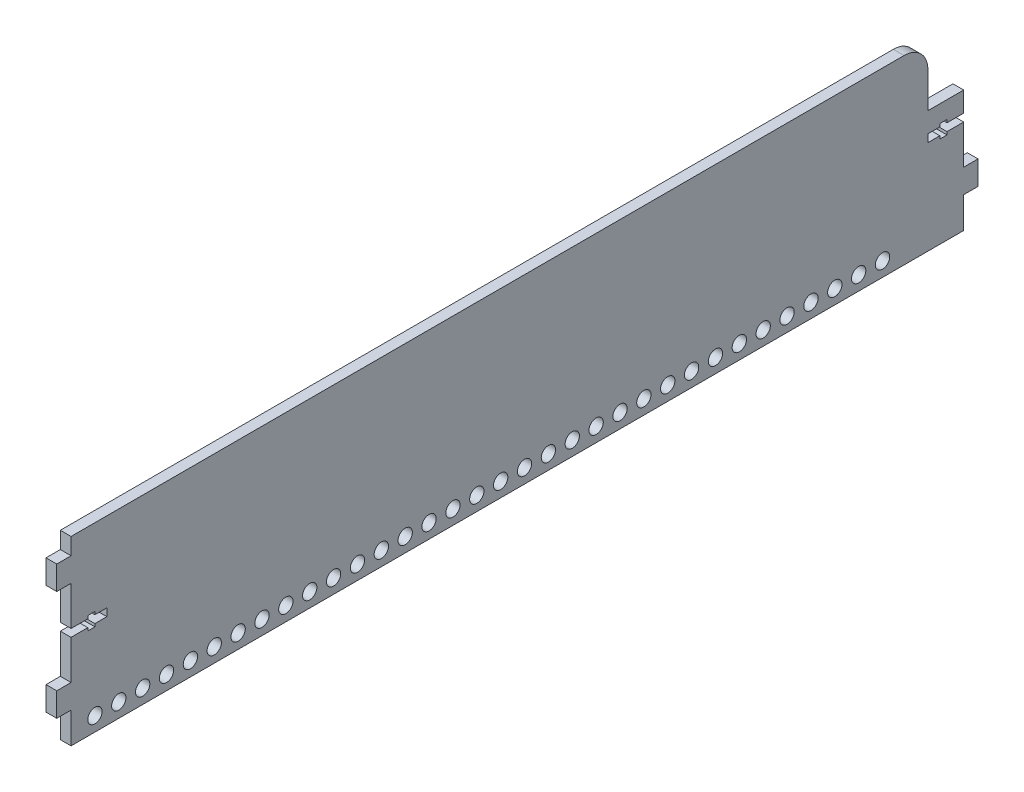
SolidWorks part; units mm, degrees
ref_plane "Front Plane" through (0, 0, 0) normal (0, 0, 1) x (1, 0, 0)
ref_plane "Top Plane" through (0, 0, 0) normal (0, 1, 0) x (1, 0, 0)
ref_plane "Right Plane" through (0, 0, 0) normal (1, 0, 0) x (0, 0, -1)
sketch "Sketch1" plane through (0, 0, 0) normal (1, 0, 0) x (0, 0, -1)
  line L1 (-187, -40) -> (187, -40)
  line L2 (-187, -40) -> (-187, 40)
  line L3 (-187, 40) -> (187, 40)
  line L4 (187, -40) -> (187, 40)
  line L5 (-187, -40) -> (187, 40) construction
  line L6 (-187, 40) -> (187, -40) construction
  point P0 (0, 0)
  dimension "D1" = 80
  dimension "D2" = 374
extrude "Boss-Extrude1" add sketch "Sketch1" along normal blind 4.5
sketch "Sketch4" plane through (0, 0, 187) normal (0, 0, 1) x (1, 0, 0)
  line L1 (4.5, 29) -> (0, 29) construction
  line L2 (4.5, 19) -> (4.5, 29) construction
  line L3 (0, 29) -> (0, 19) construction
  line L4 (0, 19) -> (4.5, 19) construction
  line L7 (4.5, -17) -> (0, -17) construction
  line L8 (4.5, -27) -> (4.5, -17) construction
  line L9 (0, -17) -> (0, -27) construction
  line L10 (0, -27) -> (4.5, -27) construction
  line L13 (4.5, 29) -> (0, 29)
  line L14 (4.5, 19) -> (4.5, 29)
  line L15 (0, 29) -> (0, 19)
  line L16 (0, 19) -> (4.5, 19)
  line L17 (4.5, -17) -> (0, -17)
  line L18 (4.5, -27) -> (4.5, -17)
  line L19 (0, -17) -> (0, -27)
  line L20 (0, -27) -> (4.5, -27)
extrude "Boss-Extrude2" add sketch "Sketch4" along normal blind 6
sketch "Sketch5" plane through (0, 0, 0) normal (-1, 0, 0) x (0, 0, 1)
  line L0 (187, 19) -> (187, -17) construction
  line L7 (0, 0) -> (0, -20.5925) construction
  line L8 (-187, 2.6) -> (-180, 2.6)
  line L9 (-177, 3.8) -> (-180, 3.8)
  line L10 (-177, 2.6) -> (-172, 2.6)
  line L11 (-172, -0.6) -> (-172, 2.6)
  line L12 (-177, -0.6) -> (-172, -0.6)
  line L13 (-177, -1.8) -> (-180, -1.8)
  line L14 (-187, -0.6) -> (-180, -0.6)
  line L15 (-180, -1.8) -> (-180, -0.6)
  line L16 (-180, 2.6) -> (-180, 3.8)
  line L17 (-177, 2.6) -> (-177, 3.8)
  line L18 (-177, -1.8) -> (-177, -0.6)
  line L19 (193, -0.6) -> (193, 2.6) construction
  line L20 (193, -0.6) -> (193, 2.6)
  line L21 (193, 1) -> (146.4296, 1) construction
  line L25 (187, -0.6) -> (187, 2.6)
  line L26 (177, -1.8) -> (177, -0.6)
  line L27 (177, 2.6) -> (177, 3.8)
  line L28 (180, 2.6) -> (180, 3.8)
  line L29 (180, -1.8) -> (180, -0.6)
  line L30 (187, -0.6) -> (180, -0.6)
  line L31 (177, -1.8) -> (180, -1.8)
  line L32 (177, -0.6) -> (172, -0.6)
  line L33 (172, -0.6) -> (172, 2.6)
  line L34 (177, 2.6) -> (172, 2.6)
  line L35 (177, 3.8) -> (180, 3.8)
  line L36 (187, 2.6) -> (180, 2.6)
  line L37 (-187, -0.6) -> (-187, 2.6)
  line L38 (-193, -0.6) -> (-193, 2.6)
  point P0 (187, 1)
  dimension "D1" = 15
  dimension "D2" = 5.6
  dimension "D3" = 3.2
  dimension "D4" = 7
  dimension "D5" = 3
extrude "Cut-Extrude3" cut sketch "Sketch5" against normal up to next contours L25 L36 L28 L35 L27 L34 L33 L32 L26 L31 L29 L30 | L37 L14 L15 L13 L18 L12 L11 L10 L17 L9 L16 L8 region at (0, 1, -179.3696) region at (0, 1, 179.3696)
sketch "Sketch7" plane through (0, 0, -187) normal (0, 0, -1) x (-1, 0, 0)
  line L6 (-4.5, -17) -> (0, -17)
  line L7 (-4.5, -17) -> (-4.5, -27)
  line L8 (-4.5, -27) -> (0, -27)
  line L9 (0, -17) -> (0, -27)
  line L15 (-4.5, -40) -> (-4.5, -0.6) construction
  line L16 (0, -40) -> (0, -0.6) construction
  line L17 (-4.5, -17) -> (0, -17) construction
  line L18 (0, -27) -> (-4.5, -27) construction
extrude "Boss-Extrude3" add sketch "Sketch7" along normal blind 6
sketch "Sketch8" plane through (0, 40, 0) normal (0, 1, 0) x (1, 0, 0)
  line L1 (0, 187) -> (4.5, 187)
  line L2 (0, 187) -> (0, -187)
  line L3 (0, -187) -> (4.5, -187)
  line L4 (4.5, 187) -> (4.5, -187)
extrude "Cut-Extrude4" cut sketch "Sketch8" against normal blind 4
sketch "Sketch9" plane through (0, 36, 0) normal (0, 1, 0) x (1, 0, 0)
  line L0 (0, 187) -> (0, -187) construction
  line L1 (0, 187) -> (4.5, 187)
  line L2 (0, 187) -> (0, 172)
  line L3 (0, 172) -> (4.5, 172)
  line L4 (4.5, 187) -> (4.5, 172)
  line L5 (4.5, -187) -> (4.5, 187) construction
  dimension "D2" = 15
extrude "Cut-Extrude5" cut sketch "Sketch9" against normal blind 25
fillet "Fillet1" radius 10 1 edges at (2.25, 36, -172)
sketch "Sketch10" plane through (0, 0, 0) normal (-1, 0, 0) x (0, 0, 1)
  line L0 (187, -40) -> (-187, -40) construction
  line L1 (187, -27) -> (187, -40) construction
  circle A0 centre (177, -34) radius 3
  circle A1 centre (167, -34) radius 3
  circle A2 centre (157, -34) radius 3
  circle A3 centre (147, -34) radius 3
  circle A4 centre (137, -34) radius 3
  circle A5 centre (127, -34) radius 3
  circle A6 centre (117, -34) radius 3
  circle A7 centre (107, -34) radius 3
  circle A8 centre (97, -34) radius 3
  circle A9 centre (87, -34) radius 3
  circle A10 centre (77, -34) radius 3
  circle A11 centre (67, -34) radius 3
  circle A12 centre (57, -34) radius 3
  circle A13 centre (47, -34) radius 3
  circle A14 centre (37, -34) radius 3
  circle A15 centre (27, -34) radius 3
  circle A16 centre (17, -34) radius 3
  circle A17 centre (7, -34) radius 3
  circle A18 centre (-3, -34) radius 3
  circle A19 centre (-13, -34) radius 3
  circle A20 centre (-23, -34) radius 3
  circle A21 centre (-33, -34) radius 3
  circle A22 centre (-43, -34) radius 3
  circle A23 centre (-53, -34) radius 3
  circle A24 centre (-63, -34) radius 3
  circle A25 centre (-73, -34) radius 3
  circle A26 centre (-83, -34) radius 3
  circle A27 centre (-93, -34) radius 3
  circle A28 centre (-103, -34) radius 3
  circle A29 centre (-113, -34) radius 3
  circle A30 centre (-123, -34) radius 3
  circle A31 centre (-133, -34) radius 3
  circle A32 centre (-143, -34) radius 3
  circle A33 centre (-153, -34) radius 3
  dimension "D1" = 6
  dimension "D2" = 6
  dimension "D3" = 10
  dimension "D4" = 34
extrude "Cut-Extrude6" cut sketch "Sketch10" against normal up to next (4.5 mm away)
